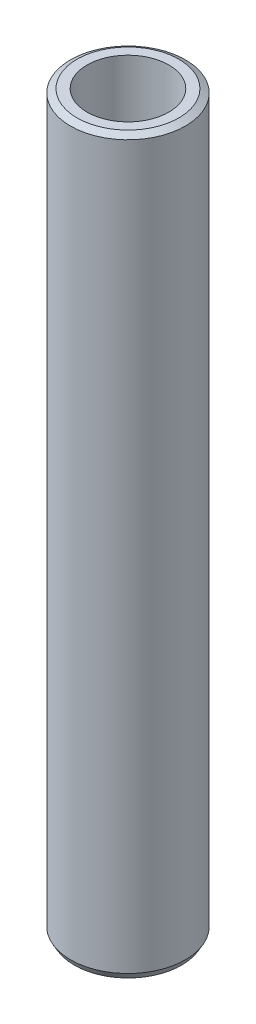
SolidWorks part; units mm, degrees
ref_plane "Front Plane" through (0, 0, 0) normal (0, 0, 1) x (1, 0, 0)
ref_plane "Top Plane" through (0, 0, 0) normal (0, 1, 0) x (1, 0, 0)
ref_plane "Right Plane" through (0, 0, 0) normal (1, 0, 0) x (0, 0, -1)
sketch "Sketch1" plane through (0, 0, 0) normal (0, 1, 0) x (1, 0, 0)
  circle A0 centre (0, 0) radius 45
  dimension "SHAFT_OD" = 90
extrude "Boss-Extrude1" add sketch "Sketch1" along normal blind 573.6103
sketch "Sketch2" plane through (0, 0, 0) normal (0, 1, 0) x (1, 0, 0)
  circle A0 centre (0, 0) radius 32.0349
  dimension "BORE_D" = 64.0699
extrude "Cut-Extrude1" cut sketch "Sketch2" along normal through all
chamfer "Chamfer1" distance 2.9617 angle 60 2 edges at (0, 573.6103, 45) (0, 0, 45) first distance on face at (0, 573.6103, 45) first distance on face at (0, 0, 32.0349)
